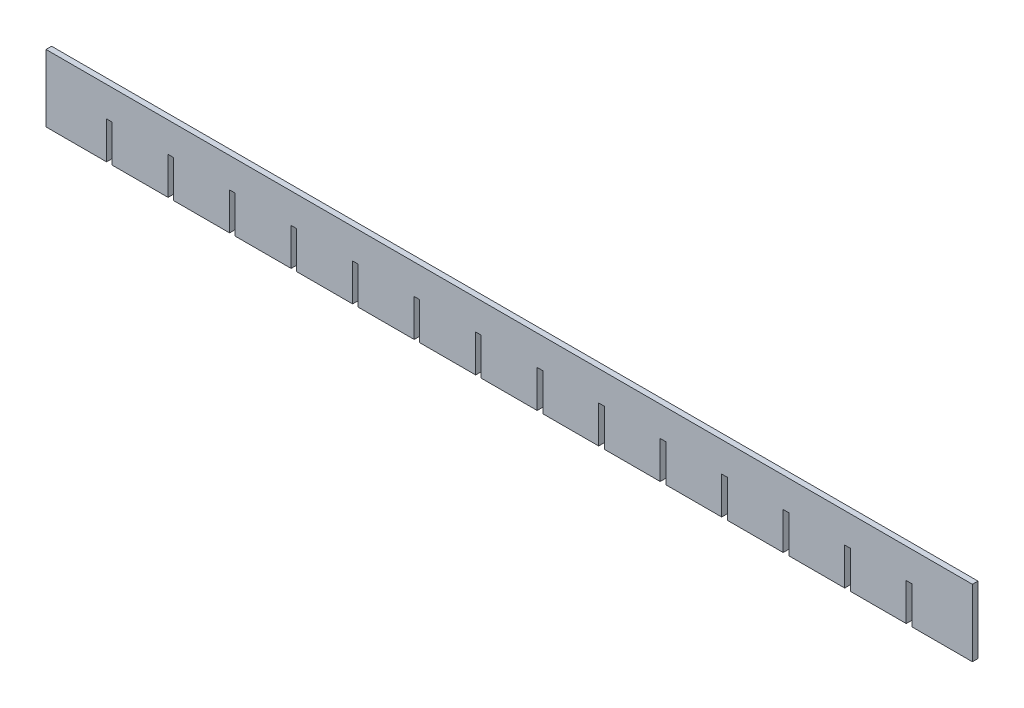
SolidWorks part; units mm, degrees
ref_plane "Ebene vorne" through (0, 0, 0) normal (0, 0, 1) x (1, 0, 0)
ref_plane "Ebene oben" through (0, 0, 0) normal (0, 1, 0) x (1, 0, 0)
ref_plane "Ebene rechts" through (0, 0, 0) normal (1, 0, 0) x (0, 0, -1)
sketch "Sketch1" plane through (0, 0, 0) normal (0, 0, 1) x (1, 0, 0)
  line L1 (-248.5, -18) -> (248.5, -18)
  line L2 (-248.5, -18) -> (-248.5, 18)
  line L3 (-248.5, 18) -> (248.5, 18)
  line L4 (248.5, -18) -> (248.5, 18)
  line L5 (-248.5, -18) -> (248.5, 18) construction
  line L6 (-248.5, 18) -> (248.5, -18) construction
  point P0 (0, 0)
  dimension "D1" = 36
  dimension "D2" = 497
extrude "Boss-Extrude1" add sketch "Sketch1" along normal blind 3
sketch "Sketch2" plane through (0, 0, 3) normal (0, 0, 1) x (1, 0, 0)
  line L6 (-248.5, -18) -> (-216, -18)
  line L7 (-248.5, -18) -> (248.5, -18) construction
  line L8 (-216, -18) -> (-216, 2)
  line L9 (-216, 2) -> (-213, 2)
  line L10 (-213, 2) -> (-213, -18)
  line L11 (-216, -18) -> (-213, -18)
  point P4 (-214.5, -18)
  dimension "D1" = 34
  dimension "D2" = 20
  dimension "D3" = 3
extrude "Cut-Extrude1" cut sketch "Sketch2" against normal through all contours L11 L10 L9 L8
pattern_linear "LPattern1" count 14 spacing 33 along (1, 0, 0) of "Cut-Extrude1"
